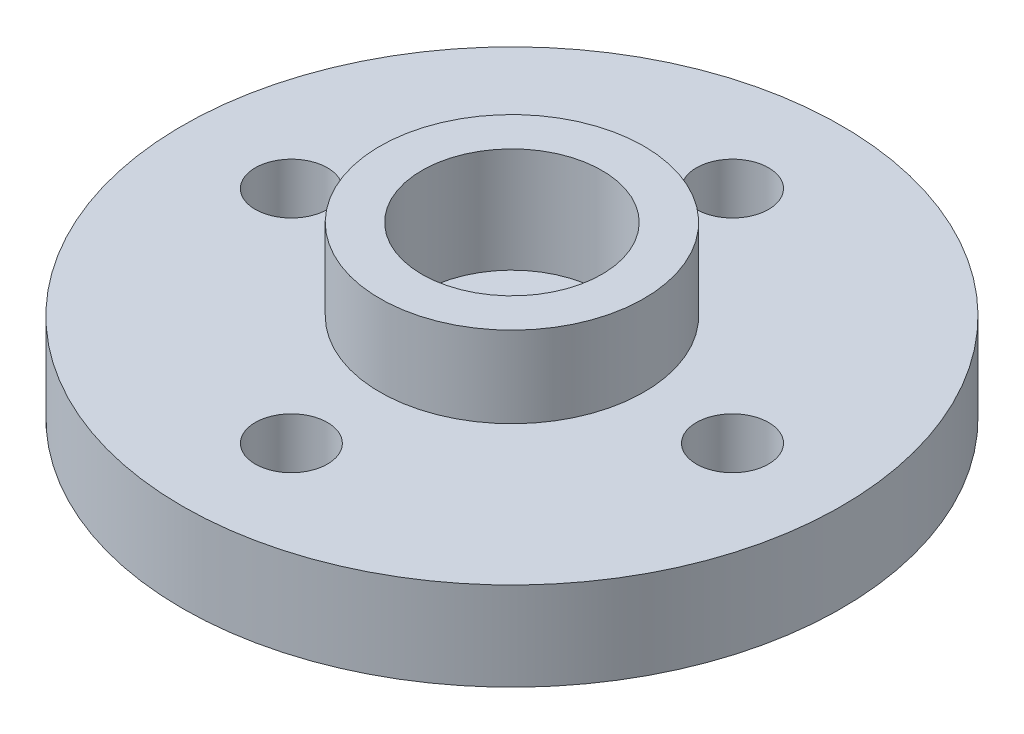
SolidWorks part; units mm, degrees
ref_plane "Alzado" through (0, 0, 0) normal (0, 0, 1) x (1, 0, 0)
ref_plane "Planta" through (0, 0, 0) normal (0, 1, 0) x (1, 0, 0)
ref_plane "Vista lateral" through (0, 0, 0) normal (1, 0, 0) x (0, 0, -1)
sketch "Croquis base" plane through (0, 0, 0) normal (0, 1, 0) x (1, 0, 0)
  line L0 (-10.9823, 0) -> (10.9823, 0) construction
  circle A0 centre (0, 0) radius 10.9823
  circle A1 centre (0, 0) radius 3.1378
  circle A2 centre (0, 0) radius 1.5689
  circle A3 centre (-7.35, 0) radius 1.2028
  circle A4 centre (0, 7.35) radius 1.2028
  circle A5 centre (7.35, 0) radius 1.2028
  circle A6 centre (0, -7.35) radius 1.2028
  dimension "D1" = 7.35
  dimension "D2" = 4
extrude "Saliente-Extruir1" add sketch "Croquis base" along normal blind 2.95 contours A0
extrude "Cortar-Extruir1" cut sketch "Croquis base<3>" along normal blind 2.95 contours A5 | A4 | A2 | A3 | A6
sketch "Croquis base<3>" plane through (0, 0, 0) normal (0, 1, 0) x (1, 0, 0) same geometry as "Croquis base"
extrude "Cortar-Extruir2" cut sketch "Croquis base<4>" along normal blind 1.05 contours A1
sketch "Croquis base<4>" plane through (0, 0, 0) normal (0, 1, 0) x (1, 0, 0) same geometry as "Croquis base"
sketch "Croquis2" plane through (0, 2.95, 0) normal (0, 1, 0) x (1, 0, 0)
  circle A0 centre (0, 0) radius 4.4
extrude "Saliente-Extruir2" add sketch "Croquis2" along normal blind 2.7
sketch "Croquis3" plane through (0, 5.65, 0) normal (0, 1, 0) x (1, 0, 0)
  circle A0 centre (0, 0) radius 3
extrude "Cortar-Extruir3" cut sketch "Croquis3" against normal blind 3.5
